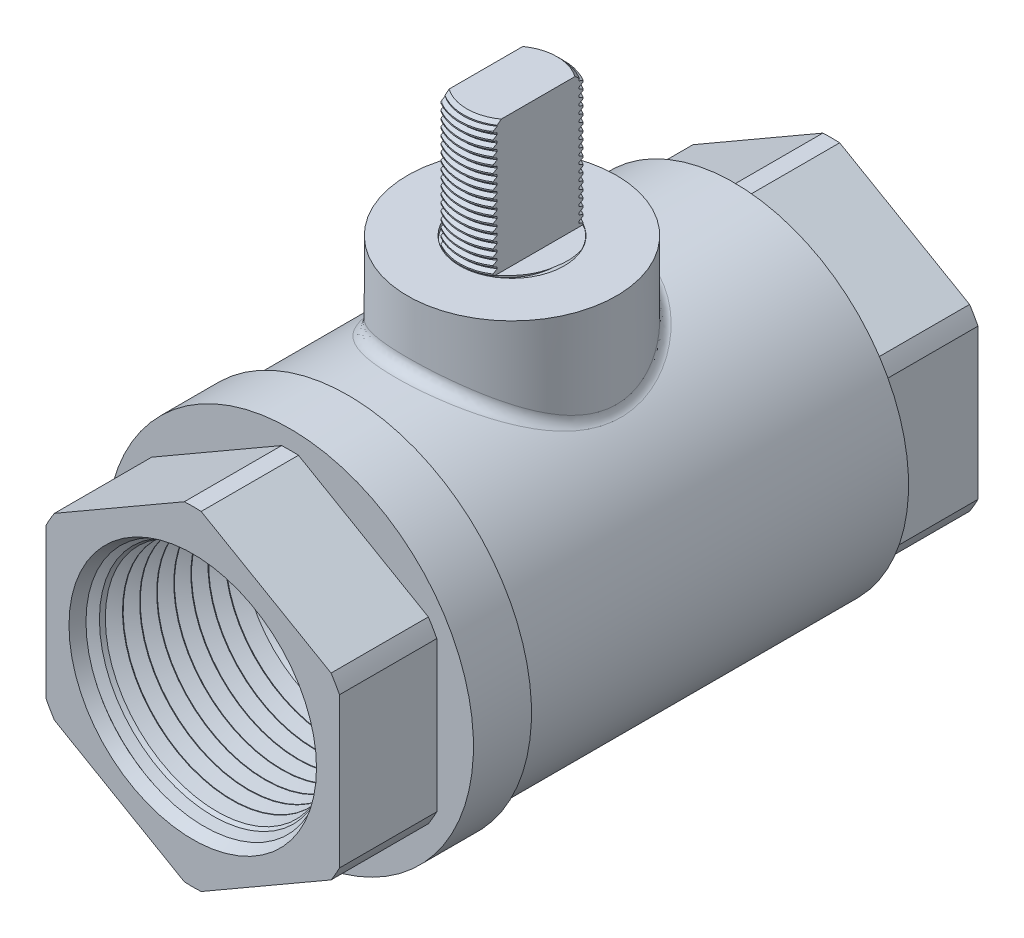
SolidWorks part; units mm, degrees
material "AISI 316 Stainless Steel Sheet (SS)"
ref_plane "Front" through (0, 0, 0) normal (0, 0, 1) x (1, 0, 0)
ref_plane "Top" through (0, 0, 0) normal (0, 1, 0) x (1, 0, 0)
ref_plane "Right" through (0, 0, 0) normal (1, 0, 0) x (0, 0, -1)
sketch "Sketch1" plane through (0, -2.9295, 125.5668) normal (1, 0, 0) x (0, 0, -1)
  line L0 (143.4992, 2.9295) -> (143.4992, 14.4244)
  line L1 (143.4992, 14.4244) -> (144.3569, 16.0232) construction
  line L2 (144.3569, 16.0232) -> (145.3126, 14.4811) construction
  line L3 (145.3126, 14.4811) -> (146.1703, 16.0799) construction
  line L4 (146.1703, 16.0799) -> (147.126, 14.5378) construction
  line L5 (145.3453, 14.542) -> (146.1376, 16.0189)
  line L6 (146.1376, 16.0189) -> (146.2067, 16.0211)
  line L7 (146.2067, 16.0211) -> (147.0896, 14.5965)
  line L8 (147.0896, 14.5965) -> (147.1587, 14.5987)
  line L9 (143.4992, 14.4244) -> (147.126, 14.5378) construction
  line L10 (144.3569, 16.0232) -> (146.1703, 16.0799) construction
  line L11 (143.9281, 15.2238) -> (146.6482, 15.3088) construction
  line L12 (143.4992, 2.9295) -> (125.5668, 2.9295) construction
  line L13 (147.1587, 14.5987) -> (147.951, 16.0756)
  line L14 (143.5319, 14.4854) -> (144.3242, 15.9622)
  line L15 (144.3242, 15.9622) -> (144.3933, 15.9644)
  line L16 (144.3933, 15.9644) -> (145.2762, 14.5399)
  line L17 (145.2762, 14.5399) -> (145.3453, 14.542)
  line L18 (143.9281, 15.2238) -> (143.4992, 15.2104) construction
  line L19 (143.4992, 15.2104) -> (143.4992, 14.4244) construction
  line L20 (143.9281, -9.3648) -> (143.4992, -9.3514) construction
  line L21 (143.5319, 14.4854) -> (143.4992, 14.4244)
  line L22 (147.951, 16.0756) -> (148.0201, 16.0777)
  line L23 (148.0201, 16.0777) -> (148.903, 14.6532)
  line L24 (148.903, 14.6532) -> (148.9721, 14.6554)
  line L25 (148.9721, 14.6554) -> (149.7644, 16.1323)
  line L26 (149.7644, 16.1323) -> (149.8335, 16.1344)
  line L27 (149.8335, 16.1344) -> (150.7164, 14.7099)
  line L28 (150.7164, 14.7099) -> (150.7855, 14.712)
  line L29 (150.7855, 14.712) -> (151.5778, 16.1889)
  line L30 (151.5778, 16.1889) -> (151.6469, 16.1911)
  line L31 (151.6469, 16.1911) -> (152.5298, 14.7666)
  line L32 (152.5298, 14.7666) -> (152.5989, 14.7687)
  line L33 (152.5989, 14.7687) -> (153.3912, 16.2456)
  line L34 (153.3912, 16.2456) -> (153.4603, 16.2478)
  line L35 (153.4603, 16.2478) -> (154.3432, 14.8232)
  line L36 (154.3432, 14.8232) -> (154.4123, 14.8254)
  line L37 (154.4123, 14.8254) -> (155.2046, 16.3023)
  line L38 (155.2046, 16.3023) -> (155.2737, 16.3044)
  line L39 (155.2737, 16.3044) -> (156.1566, 14.8799)
  line L40 (156.1566, 14.8799) -> (156.2257, 14.8821)
  line L41 (156.2257, 14.8821) -> (157.018, 16.3589)
  line L42 (157.018, 16.3589) -> (157.0871, 16.3611)
  line L43 (157.0871, 16.3611) -> (157.97, 14.9366)
  line L44 (157.97, 14.9366) -> (158.0391, 14.9387)
  line L45 (158.0391, 14.9387) -> (158.8314, 16.4156)
  line L46 (158.8314, 16.4156) -> (158.9005, 16.4178)
  line L47 (158.9005, 16.4178) -> (159.7834, 14.9932)
  line L48 (159.7834, 14.9932) -> (159.8525, 14.9954)
  line L49 (159.8525, 14.9954) -> (160.6448, 16.4723)
  line L50 (160.6448, 16.4723) -> (160.7139, 16.4744)
  line L51 (160.7139, 16.4744) -> (161.5968, 15.0499)
  line L52 (161.5968, 15.0499) -> (161.6659, 15.0521)
  line L53 (161.6659, 15.0521) -> (162.4582, 16.529)
  line L54 (162.4582, 16.529) -> (162.5273, 16.5311)
  line L55 (162.5273, 16.5311) -> (163.4102, 15.1066)
  line L56 (163.4102, 15.1066) -> (163.4793, 15.1087)
  line L57 (163.4793, 15.1087) -> (164.2716, 16.5856)
  line L58 (164.2716, 16.5856) -> (164.3407, 16.5878)
  line L59 (164.3407, 16.5878) -> (165.2236, 15.1633)
  line L60 (165.2236, 15.1633) -> (165.2927, 15.1654)
  line L61 (165.2927, 15.1654) -> (166.085, 16.6423)
  line L62 (166.085, 16.6423) -> (166.1541, 16.6445)
  line L63 (166.1541, 16.6445) -> (167.037, 15.2199)
  line L64 (167.037, 15.2199) -> (167.1061, 15.2221)
  line L65 (167.1061, 15.2221) -> (167.8984, 16.699)
  line L66 (167.8984, 16.699) -> (167.9675, 16.7011)
  line L67 (167.9675, 16.7011) -> (168.8504, 15.2766)
  line L68 (168.8504, 15.2766) -> (168.9195, 15.2788)
  line L69 (168.9195, 15.2788) -> (169.7118, 16.7556)
  line L70 (169.7118, 16.7556) -> (169.7809, 16.7578)
  line L71 (169.7809, 16.7578) -> (170.6638, 15.3333)
  line L72 (170.6638, 15.3333) -> (170.7329, 15.3354)
  line L73 (143.4992, 2.9295) -> (170.7329, 2.9295)
  line L74 (170.7329, 2.9295) -> (170.7329, 15.3354)
  line L75 (144.3587, 15.9633) -> (144.3569, 16.0232) construction
  line L76 (146.6482, 15.3088) -> (157.3676, 15.6438) construction
  line L77 (157.3676, 15.6438) -> (157.3676, 2.9295) construction
  line L78 (157.3676, 15.6438) -> (160.4918, 15.7414) construction
  line L79 (160.4918, 15.7414) -> (160.4918, 2.9295) construction
  line L84 (157.3676, 14.9177) -> (160.4918, 15.0154) construction
  line L85 (143.4992, 8.677) -> (125.5668, 8.677) construction
  line L86 (125.5668, 8.677) -> (125.5668, 2.9295) construction
  dimension "D1" = 60
  dimension "E0" = 24.5618
  dimension "Thread Pitch" = 1.8143
  dimension "D4" = 3.58
  dimension "L2 Thread Engagement" = 13.8684
  dimension "l Thread Length" = 16.9926
  dimension "Body Length" = 69.85
revolve "Revolve1" add sketch "Sketch1" angle 360 about L12
sketch "Sketch6" plane through (0, 0, 0) normal (1, 0, 0) x (0, 0, -1)
  line L0 (34.925, 0) -> (34.925, 13.538)
  line L1 (34.925, 13.538) -> (45.1661, 13.8581)
  line L2 (45.1661, 13.8581) -> (45.1661, 0)
  line L3 (45.1661, 0) -> (34.925, 0)
  line L4 (34.925, 12.8119) -> (34.925, 0) construction
  line L5 (17.9324, 0) -> (45.1661, 0) construction
  line L6 (45.1661, 0) -> (45.1661, 12.4059) construction
  line L7 (35.0779, 13.5428) -> (35.1471, 13.5449) construction
revolve "Cut-Revolve3" cut sketch "Sketch6" angle 360 about L3
sketch "Sketch7" plane through (0, 0, 0) normal (1, 0, 0) x (0, 0, -1)
  line L0 (31.8008, 11.9882) -> (34.925, 13.538)
  line L1 (34.925, 13.538) -> (34.925, 12.0859)
  line L2 (34.925, 12.0859) -> (31.8008, 11.9882)
  line L3 (34.925, 12.8119) -> (34.925, 0) construction
  line L4 (18.7573, 13.0327) -> (18.8265, 13.0349) construction
  line L5 (31.8008, 11.9882) -> (34.925, 12.0859) construction
  line L6 (17.9324, 0) -> (31.8008, 0) construction
  line L7 (31.8008, 0) -> (31.8008, 11.9882) construction
  line L8 (17.9324, 0) -> (17.9324, 11.4949) construction
  line L9 (0, 0) -> (17.9324, 0)
  line L10 (0, 0) -> (0, 10.16)
  line L11 (0, 10.16) -> (16.5975, 10.16)
  line L12 (17.9324, 0) -> (17.9324, 11.4949)
  line L13 (17.9324, 11.4949) -> (16.5975, 10.16)
  dimension "D1" = 45
  dimension "Min ID" = 20.32
revolve "Revolve3" add sketch "Sketch7" angle 360 about L6
mirror "Mirror2" about plane through (0, 0, 0) normal (0, 0, 1) of bodies 114
sketch "Sketch8" plane through (0, 0, 34.925) normal (0, 0, 1) x (1, 0, 0)
  line L1 (0, 18.5362) -> (-16.0528, 9.2681)
  line L2 (-16.0528, 9.2681) -> (-16.0528, -9.2681)
  line L3 (-16.0528, -9.2681) -> (0, -18.5362)
  line L4 (0, -18.5362) -> (16.0528, -9.2681)
  line L5 (16.0528, -9.2681) -> (16.0528, 9.2681)
  line L6 (16.0528, 9.2681) -> (0, 18.5362)
  circle A0 centre (0, 0) radius 16.0528 construction
  dimension "Body Hex" = 32.1056
extrude "Extrude1" add sketch "Sketch8" against normal up to surface (69.85 mm away) separate body up to face at (13.538, 0, -34.925)
sketch "Sketch9" plane through (0, 0, 0) normal (1, 0, 0) x (0, 0, -1)
  line L0 (-24.2824, 9.2681) -> (-24.2824, 20.066)
  line L1 (-24.2824, 20.066) -> (-17.9324, 20.066)
  line L2 (-17.9324, 20.066) -> (-17.9324, 19.5009)
  line L3 (-17.9324, 19.5009) -> (-17.5328, 19.1013)
  line L4 (-17.5328, 19.1013) -> (24.2824, 19.1013)
  line L5 (24.2824, 19.1013) -> (24.2824, 9.2681)
  line L6 (24.2824, 9.2681) -> (-24.2824, 9.2681)
  line L7 (34.925, 9.2681) -> (-34.925, 9.2681) construction
  line L8 (0, 0) -> (0, 9.2681) construction
  line L9 (17.9324, 0) -> (17.9324, 11.4949) construction
  line L10 (0, 0) -> (-24.2824, 0) construction
  line L11 (-24.2824, 0) -> (-24.2824, 9.2681) construction
  line L12 (-17.5328, 19.1013) -> (-17.5328, 18.5362) construction
  line L13 (34.925, 18.5362) -> (-34.925, 18.5362) construction
  line L14 (34.925, 12.8119) -> (34.925, 19.1013) construction
  line L15 (34.925, 19.1013) -> (24.2824, 19.1013) construction
  dimension "D1" = 6.35
  dimension "D2" = 40.132
  dimension "D3" = 135
  dimension "D4" = 6.35
revolve "Revolve4" add sketch "Sketch9" angle 360 about L10
sketch "Sketch10" plane through (0, 0, 0) normal (1, 0, 0) x (0, 0, -1)
  line L0 (0, 1.27) -> (0, 25.4259)
  line L1 (5.7023, 26.2133) -> (5.7277, 26.2133) construction
  line L2 (11.43, 26.2133) -> (11.43, 1.27)
  line L3 (11.43, 1.27) -> (0, 1.27)
  line L4 (0, 0) -> (0, 1.27) construction
  line L5 (-12.7, 21.3873) -> (-12.7, 26.4673) construction
  line L6 (-12.7, 26.4673) -> (12.7, 26.4673) construction
  line L7 (12.7, 26.4673) -> (55.4625, 46.4078) construction
  line L8 (-12.7, 21.3873) -> (-15.875, 21.3873) construction
  line L9 (-15.875, 21.3873) -> (-15.875, 29.6423) construction
  line L10 (-15.875, 29.6423) -> (11.9961, 29.6423) construction
  line L11 (11.9961, 29.6423) -> (55.4625, 49.911) construction
  line L12 (55.4625, 49.911) -> (55.4625, 46.4078) construction
  line L13 (24.2824, 19.1013) -> (-17.5328, 19.1013) construction
  line L14 (55.4625, 51.816) -> (55.4625, 44.5028) construction
  line L15 (55.4625, 44.5028) -> (127, 44.5028) construction
  line L16 (127, 44.5028) -> (127, 51.816) construction
  line L17 (127, 51.816) -> (55.4625, 51.816) construction
  line L18 (-1.9394, 29.6423) -> (-1.9394, 26.4673) construction
  line L19 (33.7293, 39.7766) -> (35.0711, 36.8991) construction
  line L20 (-11.43, 26.2133) -> (-11.43, 1.27) construction
  line L22 (55.4625, 44.5028) -> (55.4625, 10.1859) construction
  line L23 (24.2824, 19.1013) -> (-17.5328, 19.1013) construction
  line L26 (5.7023, 26.2133) -> (5.7023, 40.6913)
  line L27 (5.7023, 40.6913) -> (0, 40.6913)
  line L28 (5.7023, 26.2133) -> (5.7023, 25.4513)
  line L29 (5.7023, 25.4513) -> (0, 25.4513)
  line L30 (0, 25.4259) -> (5.7277, 25.4259)
  line L31 (5.7277, 25.4259) -> (5.7277, 26.2133)
  line L32 (5.7277, 26.2133) -> (11.43, 26.2133)
  line L33 (0, 25.4259) -> (0, 25.4513) construction
  line L34 (0, 25.4513) -> (0, 40.6913)
  line L35 (-5.7023, 26.2133) -> (-5.7023, 40.6913) construction
  line L36 (5.7277, 25.4259) -> (5.7277, 10.1859) construction
  line L37 (5.7277, 10.1859) -> (55.4625, 10.1859) construction
  point P26 (55.4625, 48.1594)
  dimension "Handle Height" = 51.816
  dimension "Handle Length" = 127
  dimension "D3" = 22.86
  dimension "D6" = 3.175
  dimension "D7" = 1.27
  dimension "D8" = 0.254
  dimension "D9" = 1.27
  dimension "D11" = 0.0254
  dimension "D12" = 0.0254
  dimension "D13" = 15.24
  dimension "D14" = 0.762
  dimension "D2" = 1.905
  dimension "D4" = 155
  dimension "D10" = 11.4046
  dimension "D15" = 7.112
  dimension "D16" = 8.255
  dimension "D17" = 1.27
revolve "Revolve5" add sketch "Sketch10" angle 360 about L4
chamfer "Chamfer1" distance 0.762 angle 45 1 edges at (0, 40.6913, -5.7023)
fillet "Fillet5" radius 1.27 1 edges at (3.0869, 18.8502, 11.0053) type face fillet first side face at (3.0869, 18.8502, 11.0053) second side face at (3.0869, 18.8502, 11.0053)
sketch "Sketch20" plane through (0, 0, 0) normal (1, 0, 0) x (0, 0, -1)
  line L0 (5.7023, 40.6913) -> (-5.7023, 40.6913) construction
  line L1 (-5.7023, 40.6913) -> (-5.7023, 39.8975) construction
  line L2 (-5.7023, 39.8975) -> (5.7023, 40.6913) construction
  line L3 (5.7023, 40.6913) -> (5.7092, 40.5923) construction
  line L4 (5.7092, 40.5923) -> (5.7574, 39.8995)
  line L5 (5.7574, 39.8995) -> (5.3116, 40.1171)
  line L6 (5.3116, 40.1171) -> (5.2978, 40.315)
  line L7 (5.2978, 40.315) -> (5.7092, 40.5923)
  line L8 (5.3047, 40.2161) -> (5.7333, 40.2459) construction
  line L9 (5.7023, 40.6913) -> (5.7023, 40.2437) construction
  line L10 (5.7023, 40.2437) -> (-5.7023, 39.45) construction
  line L11 (-5.7023, 39.45) -> (-5.7023, 39.8975) construction
  line L12 (-0.0588, 40.6913) -> (0.0588, 39.0024) construction
  line L13 (-5.7023, 26.2133) -> (-5.7023, 40.6913) construction
  line L14 (5.7023, 26.2133) -> (5.7023, 40.6913) construction
  line L15 (5.7023, 40.6913) -> (0, 40.6913) construction
  point P13 (0, 39.8469)
  dimension "D1" = 0.0992
  dimension "D2" = 0.1984
  dimension "D3" = 0.7937
  dimension "D4" = 60
  dimension "D5" = 0.7937
revolve "Cut-Revolve6" cut sketch "Sketch20" angle 360 about L12
pattern_linear "LPattern1" count 2 spacing 0.7937 along (0, 1, 0) count 19 spacing 0.7937 along (0, -1, 0) of "Cut-Revolve6"
sketch "Sketch26" plane through (0, 25.4259, 0) normal (0, 1, 0) x (-1, 0, 0)
  circle A1 centre (0, 0) radius 5.7277
  circle A2 centre (0, 0) radius 5.7277
  dimension "D1" = 0
extrude "Extrude8" add sketch "Sketch26" along normal blind 0.127
sketch "Sketch16" plane through (0, 0, 0) normal (1, 0, 0) x (0, 0, -1)
  line L0 (-34.925, 9.2681) -> (-34.925, 18.5362) construction
  line L1 (34.925, 18.5362) -> (24.2824, 18.5362)
  line L2 (34.925, 18.5362) -> (34.925, 18.0282)
  line L3 (34.925, 18.0282) -> (24.2824, 18.0282)
  line L4 (24.2824, 18.5362) -> (24.2824, 18.0282)
  line L5 (-34.925, 18.5362) -> (-24.2824, 18.5362)
  line L6 (-34.925, 18.5362) -> (-34.925, 18.0282)
  line L7 (-34.925, 18.0282) -> (-24.2824, 18.0282)
  line L8 (-24.2824, 18.5362) -> (-24.2824, 18.0282)
  line L9 (34.925, 18.5362) -> (34.925, 9.2681) construction
  line L10 (24.2824, -19.1013) -> (24.2824, 19.1013) construction
  line L11 (-24.2824, 20.066) -> (-24.2824, -20.066) construction
  line L12 (-24.2824, 18.5362) -> (-34.925, 18.5362) construction
  line L13 (0, 0) -> (-34.925, 0) construction
  line L14 (-34.925, 0) -> (-34.925, 18.0282) construction
  dimension "D1" = 0.508
revolve "Cut-Revolve5" cut sketch "Sketch16" angle 360 about L13
combine bodies "Combine1" operation type subtract main body 126 bodies to subtract 115
ref_plane "Plane2" through (0, 40.6913, 0) normal (0, 1, 0) x (-1, 0, 0)
sketch "Sketch27" plane through (0, 40.6913, 0) normal (0, 1, 0) x (-1, 0, 0)
  line L0 (-2.8511, -5.7023) -> (2.8511, 5.7023) construction
  line L1 (-2.8511, 5.7023) -> (2.8511, 5.7023)
  line L2 (-2.8511, 5.7023) -> (-2.8511, -5.7023)
  line L3 (-2.8511, -5.7023) -> (2.8511, -5.7023)
  line L4 (2.8511, 5.7023) -> (2.8511, -5.7023)
  dimension "D1" = 5.7023
extrude "Cut-Extrude3" cut sketch "Sketch27" against normal up to surface (14.478 mm away) flip side to cut up to face at (0, 26.2133, -5.7277)
sketch "Sketch11" plane through (0, 0, 0) normal (1, 0, 0) x (0, 0, -1)
  line L1 (11.9961, 29.6423) -> (55.4625, 49.911) construction
  line L2 (12.7, 26.4673) -> (55.4625, 46.4078) construction
  line L3 (-12.7, 26.4673) -> (12.7, 26.4673) construction
  line L4 (-12.7, 21.3873) -> (-12.7, 26.4673) construction
  line L5 (-15.875, 29.6423) -> (11.9961, 29.6423) construction
  line L6 (-15.875, 21.3873) -> (-15.875, 29.6423) construction
  line L7 (125.095, 46.4078) -> (125.095, 49.911)
  line L8 (11.9961, 29.6423) -> (55.4625, 49.911)
  line L9 (12.7, 26.4673) -> (55.4625, 46.4078)
  line L10 (-12.7, 26.4673) -> (12.7, 26.4673)
  line L11 (-12.7, 21.3873) -> (-12.7, 26.4673)
  line L12 (-15.875, 29.6423) -> (11.9961, 29.6423)
  line L13 (-15.875, 21.3873) -> (-15.875, 29.6423)
  line L14 (-12.7, 21.3873) -> (-15.875, 21.3873) construction
  line L15 (-12.7, 21.3873) -> (-15.875, 21.3873)
  line L16 (55.4625, 49.911) -> (125.095, 49.911)
  line L17 (55.4625, 46.4078) -> (125.095, 46.4078)
  line L18 (127, 44.5028) -> (127, 51.816) construction
  dimension "D1" = 1.905
ref_axis "Axis2" through (0, -23.6601, 0) along (0, 1, 0)
equation "\"D2@Sketch1\"=\"Thread Pitch@Sketch1\"*.033"
equation "\"D2@Sketch9\"=\"Body Hex@Sketch8\"*1.25"
equation "\"D1@Sketch9\" = \"Thread Pitch@Sketch1\"*3.5"
equation "\"D4@Sketch9\"=\"D1@Sketch9\""
equation "\"D2@LPattern1\"=\"D13@Sketch10\"/\"D3@Sketch20\""
